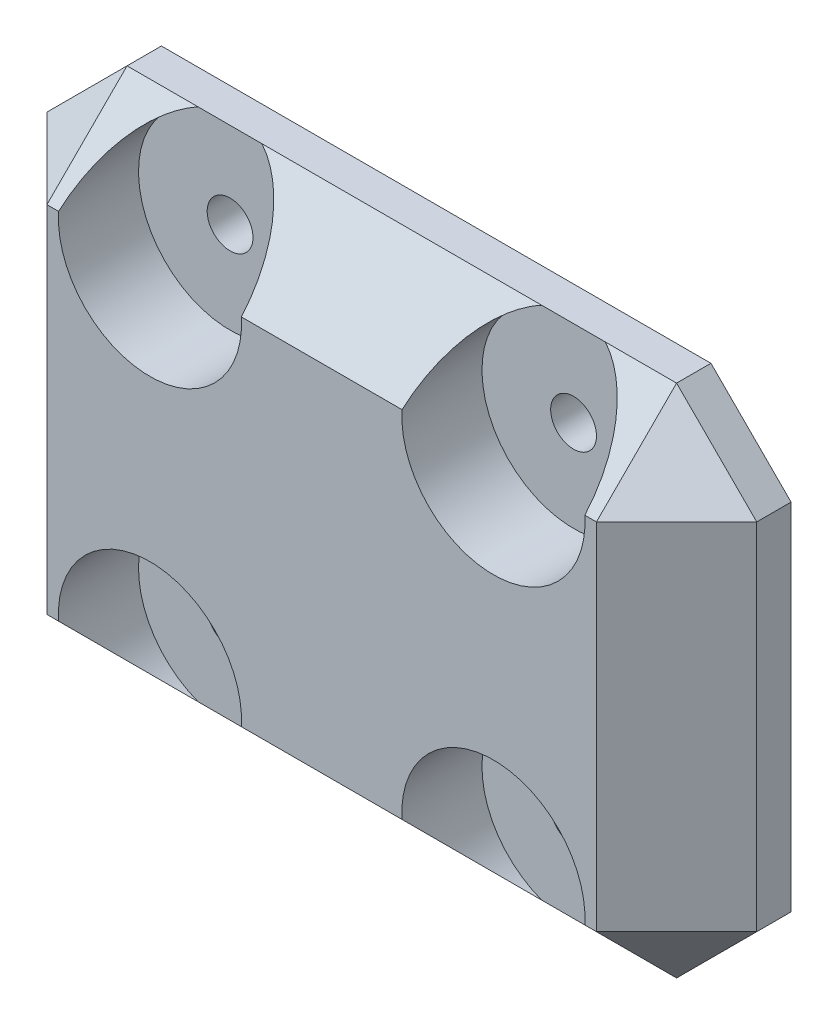
SolidWorks part; units mm, degrees
material "ABS"
ref_plane "Front Plane" through (0, 0, 0) normal (0, 0, 1) x (1, 0, 0)
ref_plane "Top Plane" through (0, 0, 0) normal (0, 1, 0) x (1, 0, 0)
ref_plane "Right Plane" through (0, 0, 0) normal (1, 0, 0) x (0, 0, -1)
sketch "Sketch1" plane through (0, 0, 0) normal (0, 0, 1) x (1, 0, 0)
  line L1 (-31, -22.5) -> (31, -22.5)
  line L2 (-31, -22.5) -> (-31, 22.5)
  line L3 (-31, 22.5) -> (31, 22.5)
  line L4 (31, -22.5) -> (31, 22.5)
  line L5 (-31, -22.5) -> (31, 22.5) construction
  line L6 (-31, 22.5) -> (31, -22.5) construction
  line L7 (15, 15) -> (-15, 15) construction
  line L8 (15, 15) -> (15, -15) construction
  line L9 (15, -15) -> (-15, -15) construction
  line L10 (-15, 15) -> (-15, -15) construction
  line L11 (15, 15) -> (-15, -15) construction
  line L12 (15, -15) -> (-15, 15) construction
  circle A0 centre (-15, -15) radius 2
  circle A1 centre (-15, 15) radius 2
  circle A2 centre (15, 15) radius 2
  circle A3 centre (15, -15) radius 2
  point P0 (0, 0)
  point P5 (0, 0)
  dimension "D5" = 4
  dimension "D6" = 4
  dimension "D7" = 4
  dimension "D8" = 4
  dimension "D1" = 62
  dimension "D2" = 45
  dimension "D3" = 30
  dimension "D4" = 30
extrude "Boss-Extrude1" add sketch "Sketch1" along normal blind 10
chamfer "Chamfer1" distance 7 angle 45 8 edges at (0, -22.5, 10) (-31, -22.5, 5) (-31, 0, 10) (-31, 22.5, 5) (0, 22.5, 10) (31, -22.5, 5) (31, 0, 10) (31, 22.5, 5)
sketch "Sketch2" plane through (0, 0, 10) normal (0, 0, 1) x (1, 0, 0)
  circle A0 centre (-15, 15) radius 8
  circle A1 centre (-15, -15) radius 8
  circle A2 centre (15, -15) radius 8
  circle A3 centre (15, 15) radius 8
  dimension "D1" = 16
  dimension "D2" = 16
  dimension "D3" = 16
  dimension "D4" = 16
extrude "Cut-Extrude1" cut sketch "Sketch2" against normal blind 7
